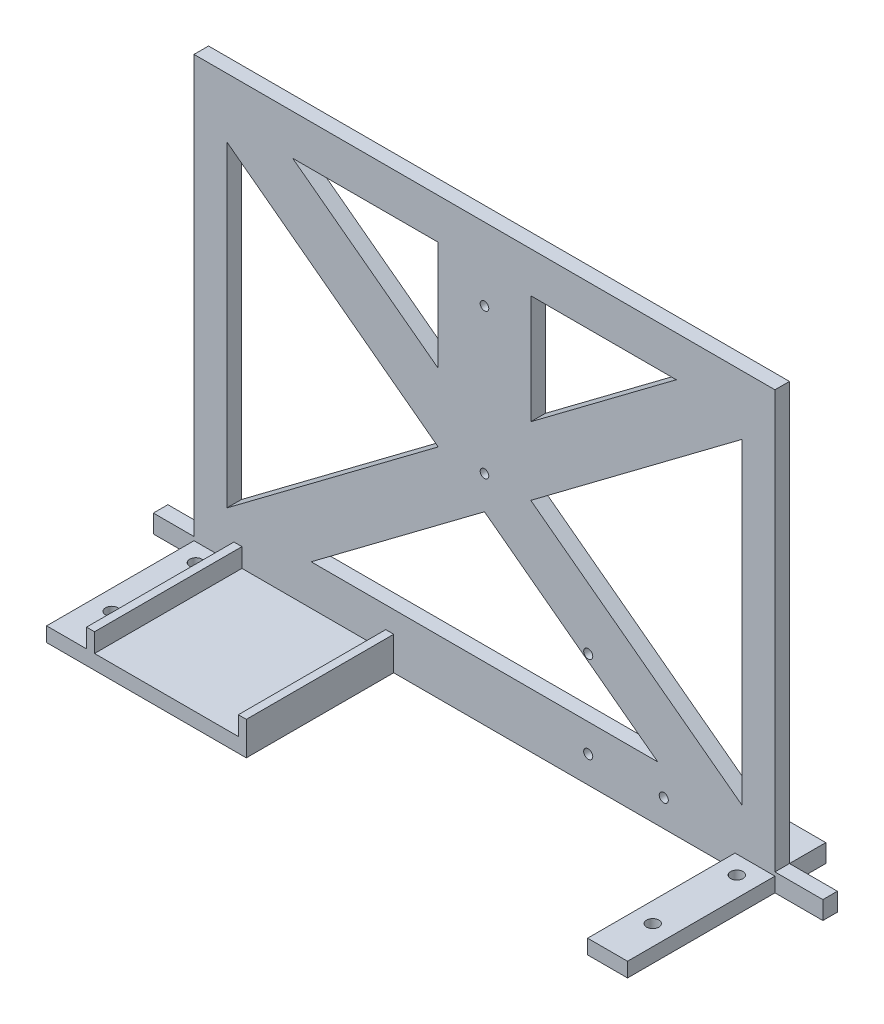
SolidWorks part; units mm, degrees
ref_plane "Front" through (0, 0, 0) normal (0, 0, 1) x (1, 0, 0)
ref_plane "Top" through (0, 0, 0) normal (0, 1, 0) x (1, 0, 0)
ref_plane "Right" through (0, 0, 0) normal (1, 0, 0) x (0, 0, -1)
sketch "Sketch1" plane through (0, 0, 0) normal (0, 0, 1) x (1, 0, 0)
  line L0 (-90.1289, 55.4552) -> (-90.1289, -55.4552)
  line L1 (-101.6, 76.2) -> (101.6, 76.2)
  line L2 (-101.6, 76.2) -> (-101.6, -76.2)
  line L3 (-101.6, -76.2) -> (101.6, -76.2)
  line L4 (101.6, 76.2) -> (101.6, -76.2)
  line L5 (-101.6, 76.2) -> (101.6, -76.2) construction
  line L6 (-101.6, -76.2) -> (101.6, 76.2) construction
  line L7 (0, -55) -> (0, 55) construction
  line L8 (-90.1289, -55.4552) -> (-16.1887, 0)
  line L9 (-16.1887, 0) -> (-90.1289, 55.4552)
  line L10 (55, 0) -> (-55, 0) construction
  line L11 (16.1887, 0) -> (90.1289, 55.4552)
  line L12 (90.1289, -55.4552) -> (16.1887, 0)
  line L13 (90.1289, 55.4552) -> (90.1289, -55.4552)
  line L14 (-16.1887, 61.9912) -> (-16.1887, 23.8125)
  line L15 (-16.1887, 23.8125) -> (-67.0937, 61.9912)
  line L16 (-67.0937, 61.9912) -> (-16.1887, 61.9912)
  line L17 (16.1887, 23.8125) -> (67.0937, 61.9912)
  line L18 (16.1887, 61.9912) -> (16.1887, 23.8125)
  line L19 (67.0937, 61.9912) -> (16.1887, 61.9912)
  line L20 (-60.6282, -57.0175) -> (0, -11.5463)
  line L21 (0, -11.5463) -> (60.6282, -57.0175)
  line L22 (60.6282, -57.0175) -> (-60.6282, -57.0175)
  circle A0 centre (0, 50.8) radius 1.5
  circle A2 centre (0, 0) radius 1.5
  point P0 (0, 0)
  dimension "D3" = 3
  dimension "D4" = 50.8
  dimension "D6" = 19.05
  dimension "D1" = 203.2
  dimension "D2" = 152.4
  dimension "D5" = 25.4
extrude "Boss-Extrude1" add sketch "Sketch1" along normal blind 5.08 contours L4 L1 L2 L3 A2 A0 L19 L17 L18 L9 L8 L0 L11 L13 L12 L15 L16 L14 L21 L22 L20 region at (0, 73.66, 0)
sketch "Sketch2" plane through (0, 0, 5.08) normal (0, 0, 1) x (1, 0, 0)
  line L0 (-101.6, -76.2) -> (101.6, -76.2) construction
  line L1 (-101.6, -76.2) -> (-87.63, -76.2)
  line L2 (-101.6, -76.2) -> (-101.6, -71.12)
  line L3 (-101.6, -71.12) -> (-87.63, -71.12)
  line L4 (-87.63, -76.2) -> (-87.63, -71.12)
  line L5 (0, -55) -> (0, 55) construction
  line L6 (101.6, -71.12) -> (87.63, -71.12)
  line L7 (87.63, -76.2) -> (87.63, -71.12)
  line L8 (101.6, -76.2) -> (87.63, -76.2)
  line L9 (101.6, -76.2) -> (101.6, -71.12)
  line L11 (-87.63, -71.12) -> (-31.75, -71.12)
  line L12 (-87.63, -71.12) -> (-87.63, -76.2)
  line L13 (-87.63, -76.2) -> (-31.75, -76.2)
  line L14 (-31.75, -71.12) -> (-31.75, -76.2)
  line L15 (-87.63, -71.12) -> (-84.836, -71.12)
  line L16 (-87.63, -71.12) -> (-87.63, -64.5258)
  line L17 (-87.63, -64.5258) -> (-84.836, -64.5258)
  line L18 (-84.836, -71.12) -> (-84.836, -64.5258)
  line L19 (-31.75, -71.12) -> (-34.544, -71.12)
  line L20 (-31.75, -71.12) -> (-31.75, -64.5258)
  line L21 (-31.75, -64.5258) -> (-34.544, -64.5258)
  line L22 (-34.544, -71.12) -> (-34.544, -64.5258)
  line M10 (-101.6, -76.2) -> (101.6, -76.2)
  dimension "D1" = 5.08
  dimension "D2" = 55.88
  dimension "D3" = 50.292
  dimension "D4" = 13.97
  dimension "D5" = 31.75
extrude "Boss-Extrude2" add sketch "Sketch2" along normal blind 51.562 contours L4 L3 L2 M10 | L14 L11 L4 M10 | L9 L6 L7 M10 | L16 L15 L18 L17 | L20 L19 L22 L21 region at (-94.615, -73.66, 5.08) region at (94.615, -73.66, 5.08) region at (-59.69, -73.66, 5.08)
sketch "Sketch3" plane through (0, -71.12, 0) normal (0, 1, 0) x (1, 0, 0)
  line L4 (0, -31.1531) -> (0, 31.1531) construction
  line L10 (-101.6, -5.08) -> (-87.63, -5.08) construction
  line L11 (-101.6, -56.642) -> (-101.6, -5.08) construction
  circle A0 centre (-94.615, -11.43) radius 2.159
  circle A1 centre (94.615, -11.43) radius 2.159
  circle A2 centre (-94.615, -40.84) radius 2.159
  circle A3 centre (94.615, -40.84) radius 2.159
  dimension "D1" = 4.318
  dimension "D4" = 29.41
  dimension "D5" = 4.318
  dimension "D6" = 4.318
  dimension "D2" = 6.35
  dimension "D3" = 6.985
extrude "Cut-Extrude1" cut sketch "Sketch3" against normal up to next contours A0 | A1 | A3 | A2 | A2 | A3 region at (-94.615, -71.12, 11.43) region at (94.615, -71.12, 11.43) region at (-94.615, -71.12, 40.84) region at (94.615, -71.12, 40.84)
sketch "Sketch4" plane through (0, 0, 0) normal (0, 0, -1) x (-1, 0, 0)
  line L0 (0, 31.1531) -> (0, -31.1531) construction
  line L1 (-101.6, -76.2) -> (-88.9, -76.2)
  line L2 (-101.6, -76.2) -> (-101.6, -69.85)
  line L3 (-101.6, -69.85) -> (-88.9, -69.85)
  line L4 (-101.6, 76.2) -> (-101.6, -76.2)
  line L5 (-101.6, -76.2) -> (101.6, -76.2)
  line L6 (101.6, -76.2) -> (101.6, 76.2)
  line L7 (101.6, 76.2) -> (-101.6, 76.2)
  line L8 (-101.6, 76.2) -> (-101.6, -76.2)
  line L9 (-101.6, -76.2) -> (101.6, -76.2)
  line L10 (101.6, -76.2) -> (101.6, 76.2)
  line L11 (101.6, 76.2) -> (-101.6, 76.2)
  line L12 (-88.9, -76.2) -> (-88.9, -69.85)
  line L13 (101.6, -69.85) -> (88.9, -69.85)
  line L14 (88.9, -76.2) -> (88.9, -69.85)
  line L15 (101.6, -76.2) -> (88.9, -76.2)
  line L16 (101.6, -76.2) -> (101.6, -69.85)
  dimension "D2" = 12.7
  dimension "D3" = 6.35
  dimension "D1" = 0
extrude "Boss-Extrude3" add sketch "Sketch4" along normal blind 12.7 contours L2 L1 L12 L3 | L16 L13 L14 L15
sketch "Sketch5" plane through (101.6, 0, 0) normal (1, 0, 0) x (0, 0, -1)
  line L1 (0, -69.85) -> (-5.08, -69.85)
  line L2 (0, -69.85) -> (0, -76.2)
  line L3 (0, -76.2) -> (-5.08, -76.2)
  line L4 (-5.08, -69.85) -> (-5.08, -76.2)
extrude "Boss-Extrude4" add sketch "Sketch5" along normal blind 16.764
sketch "Sketch6" plane through (-101.6, 0, 0) normal (-1, 0, 0) x (0, 0, 1)
  line L1 (0, -69.85) -> (5.08, -69.85)
  line L2 (0, -69.85) -> (0, -76.2)
  line L3 (0, -76.2) -> (5.08, -76.2)
  line L4 (5.08, -69.85) -> (5.08, -76.2)
extrude "Boss-Extrude5" add sketch "Sketch6" along normal blind 14.224
sketch "Sketch7" plane through (0, 0, 5.08) normal (0, 0, 1) x (1, 0, 0)
  circle A0 centre (36.2876, -66.7853) radius 1.5875
  circle A1 centre (36.2876, -36.4323) radius 1.5875
  circle A3 centre (62.7036, -66.7853) radius 1.5875
  dimension "D1" = 3.175
  dimension "D2" = 30.353
  dimension "D3" = 26.416
extrude "Cut-Extrude2" cut sketch "Sketch7" against normal up to next
